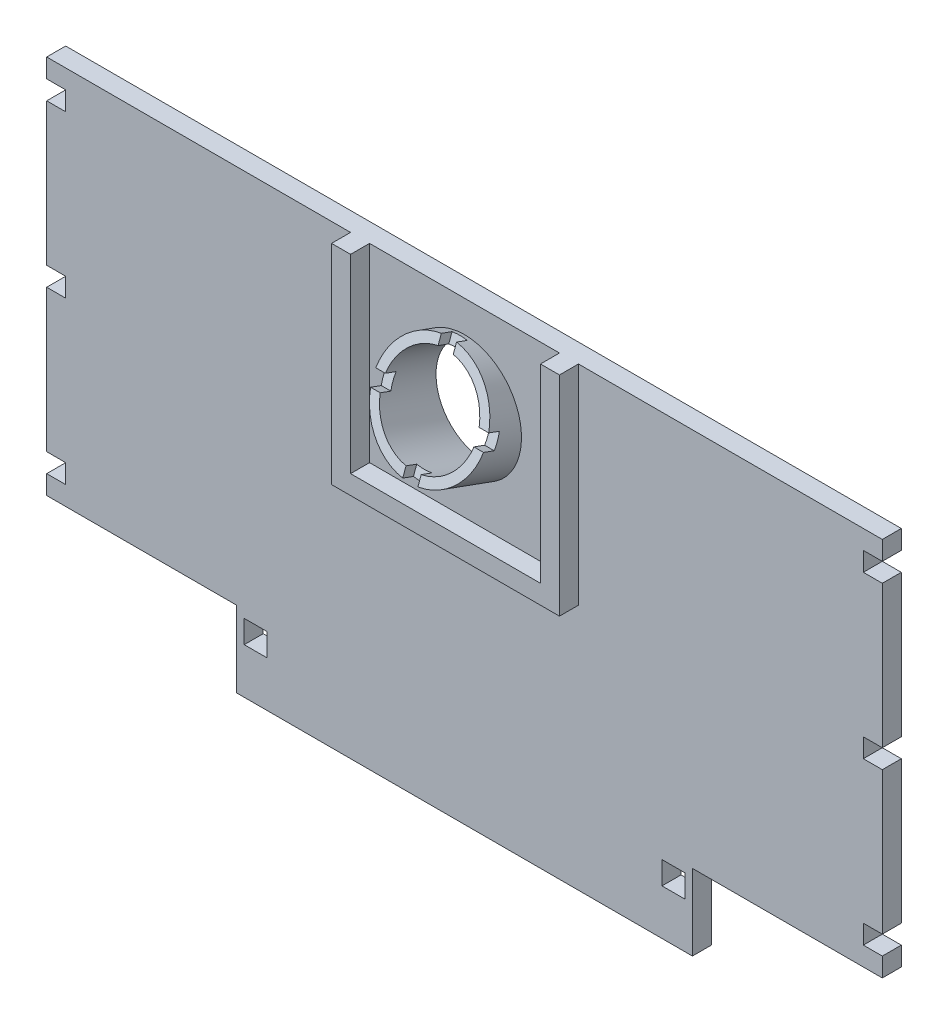
SolidWorks part; units mm, degrees
ref_plane "Front Plane" through (0, 0, 0) normal (0, 0, 1) x (1, 0, 0)
ref_plane "Top Plane" through (0, 0, 0) normal (0, 1, 0) x (1, 0, 0)
ref_plane "Right Plane" through (0, 0, 0) normal (1, 0, 0) x (0, 0, -1)
sketch "Sketch2" plane through (0, 0, 0) normal (0, 0, 1) x (1, 0, 0)
  line L0 (-100, -75) -> (-100, -45)
  line L1 (-100, 75) -> (100, 75)
  line L2 (-100, 75) -> (-100, -75)
  line L3 (-100, -75) -> (100, -75)
  line L4 (100, 75) -> (100, -75)
  line L5 (-100, 75) -> (100, -75) construction
  line L6 (-100, -75) -> (100, 75) construction
  line L7 (-100, -45) -> (-60, -45)
  line L8 (-60, -45) -> (-60, -75)
  line L9 (100, -75) -> (100, -45)
  line L10 (100, -45) -> (60, -45)
  line L11 (60, -45) -> (60, -75)
  line L12 (-60, -75) -> (-60, -65)
  line L13 (-60, -65) -> (60, -65)
  line L14 (-60, -45) -> (-50, -45)
  line L15 (-50, -45) -> (-50, -55)
  line L16 (-50, -55) -> (-60, -55)
  line L17 (60, -45) -> (50, -45)
  line L18 (50, -45) -> (50, -55)
  line L19 (50, -55) -> (60, -55)
  line L20 (-55, -55) -> (-55, -50)
  line L21 (-55, -50) -> (-50, -50)
  line L22 (-50, -45) -> (-52, -45)
  line L23 (-50, -45) -> (-50, -47)
  line L24 (0, -65) -> (0, -61.3332)
  line L25 (-58, -53) -> (-52, -53)
  line L26 (-58, -53) -> (-58, -47)
  line L27 (-58, -47) -> (-52, -47)
  line L28 (-52, -53) -> (-52, -47)
  line L29 (-58, -53) -> (-52, -47) construction
  line L30 (-58, -47) -> (-52, -53) construction
  line L31 (58, -47) -> (52, -47)
  line L32 (52, -53) -> (52, -47)
  line L33 (58, -53) -> (52, -53)
  line L34 (58, -53) -> (58, -47)
  point P0 (0, 0)
  dimension "D1" = 200
  dimension "D2" = 150
  dimension "D3" = 40
extrude "Boss-Extrude1" add sketch "Sketch2" along normal blind 5 contours L19 L18 L17 L10 L4 L1 L2 L7 L14 L15 L16 L8 L13 L11 | L18 L19 L11 L17 L34 L33 L32 L31 | L28 L21 L15 L14 L8 L16 L20 L25 L26 L27 | L28 L25 L20 L16 L15 L21 region at (0, 9.084, 0) region at (-56, -45.1414, 0) region at (-51.9375, -53.0625, 0) region at (55, -54.8586, 0)
sketch "Sketch3" plane through (0, 0, 5) normal (0, 0, 1) x (1, 0, 0)
  line L0 (-100, 75) -> (-100, -45) construction
  line L1 (-100, 75) -> (-100, 55)
  line L2 (-100, 55) -> (100, 55)
  line L3 (100, 75) -> (100, -45) construction
  line L4 (100, 55) -> (100, 75)
  line L5 (100, 75) -> (-100, 75)
extrude "Cut-Extrude1" cut sketch "Sketch3" against normal blind 5
sketch "Sketch4" plane through (0, 0, 0) normal (0, 0, -1) x (-1, 0, 0)
  line L0 (-100, 55) -> (100, 55)
  line L1 (100, 55) -> (100, -45)
  line L2 (100, -45) -> (-100, -45)
  line L3 (-100, -45) -> (-100, 55)
  line L4 (100, 55) -> (95, 55)
  line L5 (95, 55) -> (95, -45)
  line L6 (95, -45) -> (100, -45)
  line L7 (100, 55) -> (100, 45)
  line L8 (100, 45) -> (95, 45)
  line L9 (95, 45) -> (95, 50)
  line L10 (95, 50) -> (100, 50)
  line L11 (100, 50) -> (99, 50)
  line L12 (100, 50) -> (100, 49)
  line L13 (97.5, 45) -> (97.5, 47.5)
  line L14 (100, 5) -> (95, 5)
  line L15 (96, 46) -> (99, 46)
  line L16 (96, 46) -> (96, 49)
  line L17 (96, 49) -> (99, 49)
  line L18 (99, 46) -> (99, 49)
  line L19 (96, 46) -> (99, 49) construction
  line L20 (96, 49) -> (99, 46) construction
  line L21 (96, -39) -> (99, -39)
  line L22 (99, -36) -> (99, -39)
  line L23 (96, -36) -> (99, -36)
  line L24 (96, -36) -> (96, -39)
  line L25 (100, 5) -> (100, 7.5)
  line L26 (100, 5) -> (100, 2.5)
  line L27 (100, 2.5) -> (95, 2.5)
  line L28 (95, 2.5) -> (95, 7.5)
  line L29 (95, 7.5) -> (100, 7.5)
  line L30 (100, 2.5) -> (99, 2.5)
  line L31 (100, 2.5) -> (100, 3.5)
  line L32 (0, -45) -> (0, -36)
  line L33 (96, 6.5) -> (99, 6.5)
  line L34 (96, 6.5) -> (96, 3.5)
  line L35 (96, 3.5) -> (99, 3.5)
  line L36 (99, 6.5) -> (99, 3.5)
  line L37 (96, 6.5) -> (99, 3.5) construction
  line L38 (96, 3.5) -> (99, 6.5) construction
  line L39 (97.5, -36) -> (97.5, -39)
  line L40 (100, 50) -> (95, 50)
  line L41 (100, 50) -> (100, 45)
  line L42 (100, 45) -> (95, 45)
  line L43 (95, 50) -> (95, 45)
  line L44 (100, 50) -> (95, 45) construction
  line L45 (100, 45) -> (95, 50) construction
  line L46 (97.5, -39) -> (97.5, -40)
  line L47 (-100, 45) -> (-95, 45)
  line L48 (100, -35) -> (95, -35)
  line L49 (100, -35) -> (100, -40)
  line L50 (100, -40) -> (95, -40)
  line L51 (95, -35) -> (95, -40)
  line L52 (100, -35) -> (95, -40) construction
  line L53 (100, -40) -> (95, -35) construction
  line L54 (-95, 50) -> (-95, 45)
  line L55 (-100, 50) -> (-95, 50)
  line L56 (-100, 50) -> (-100, 45)
  line L57 (-100, 5) -> (-100, 7.5)
  line L58 (-95, 7.5) -> (-100, 7.5)
  line L59 (-95, 2.5) -> (-95, 7.5)
  line L60 (-100, 2.5) -> (-95, 2.5)
  line L61 (-100, 5) -> (-100, 2.5)
  line L62 (-100, -40) -> (-95, -40)
  line L63 (-95, -35) -> (-95, -40)
  line L64 (-100, -35) -> (-95, -35)
  line L65 (-100, -35) -> (-100, -40)
  point P31 (97.5, 5)
  point P44 (97.5, -37.5)
sketch "Sketch6" plane through (0, 0, 0) normal (0, 0, -1) x (-1, 0, 0)
  line L0 (0, -65) -> (0, -45)
  line L1 (60, -65) -> (-60, -65) construction
  line L2 (0, -45) -> (50, -45)
  line L3 (50, -45) -> (50, -65)
  line L4 (0, -45) -> (-50, -45)
  line L5 (-50, -45) -> (-50, -65)
  line L6 (-50, -45) -> (-60, -45)
  line M21 (-60, -65) -> (60, -65)
extrude "Boss-Extrude2" add sketch "Sketch6" along normal blind 100 contours L3 L2 L0 M21 | L4 L5 L0 M21 region at (25, -55, 0) region at (-25, -55, 0)
sketch "Sketch8" plane through (50, 0, 0) normal (1, 0, 0) x (0, 0, -1)
  line L0 (100, -45) -> (100, 55)
  line L1 (100, 55) -> (78.5761, 55)
  line L2 (100, -45) -> (42.1791, -45)
  line L3 (100, -45) -> (0, -45) construction
  line L4 (78.5761, 55) -> (42.1791, -45)
  line L5 (60.3776, 5) -> (63.7978, 14.3969)
  line L6 (60.3776, 5) -> (56.9574, -4.3969)
  line M8 (100, -45) -> (0, -45)
  dimension "D1" = 21.4239
  dimension "D2" = 57.8209
extrude "Boss-Extrude3" add sketch "Sketch8" against normal blind 100 contours L1 L4 L0 M8 region at (50, -2.655, -78.7957)
sketch "Sketch12" plane through (50, 0, 0) normal (1, 0, 0) x (0, 0, -1)
  line L0 (42.1791, -45) -> (78.5761, 55)
  line L2 (42.1791, -45) -> (100, -45)
  line L3 (100, 55) -> (100, -65) construction
  line L4 (100, -45) -> (100, 55)
  line L5 (78.5761, 55) -> (83.897, 55)
  line L6 (100, 55) -> (78.5761, 55) construction
  line L7 (83.897, 55) -> (88.897, 55)
  line L8 (83.897, 55) -> (47.5, -45)
  line L9 (88.897, 55) -> (52.5, -45)
  line M5 (100, 55) -> (78.5761, 55)
  line M6 (78.5761, 55) -> (42.1791, -45)
  dimension "D1" = 5.3209
extrude "Cut-Extrude4" cut sketch "Sketch12" against normal blind 100 contours L8 L2 M5 M6 region at (50, 5, -63.0381)
sketch "Sketch13" plane through (0, -20.5302, -56.4063) normal (0, 0.342, 0.9397) x (1, 0, 0)
  line L0 (-50, 80.3776) -> (50, 80.3776)
  line L1 (50, 80.3776) -> (50, -26.0402)
  line L2 (50, -26.0402) -> (-50, -26.0402)
  line L3 (-50, -26.0402) -> (-50, 80.3776)
  line L4 (0, 80.3776) -> (0, 27.1687)
  circle A0 centre (0, 27.1687) radius 10
extrude "Boss-Extrude5" add sketch "Sketch13" along normal blind 100 contours A0 region at (6.8711, 11.4567, -68.0486)
sketch "Sketch14" plane through (0, 13.6718, 37.563) normal (0, 0.342, 0.9397) x (1, 0, 0)
  circle A0 centre (0, 27.1687) radius 10.3
  circle A1 centre (0, 27.1687) radius 12.5
  circle M3 centre (0, 27.1687) radius 10
  dimension "D1" = 25
extrude "Cut-Extrude5" cut sketch "Sketch14" against normal blind 100 contours M3 | A1 M3 | A0 M3 | A0 | A1 region at (-10.0087, 39.202, 28.2708) region at (-12.1464, 39.202, 28.2708) region at (0, 39.202, 28.2708)
ref_plane "Plane1" through (0, 13.6718, 37.563) normal (0, 0.342, 0.9397) x (1, 0, 0)
sketch "Sketch15" plane through (0, 13.6718, 37.563) normal (0, 0.342, 0.9397) x (1, 0, 0)
  circle A0 centre (0, 27.1687) radius 10
  circle A1 centre (0, 27.1687) radius 12.5
  circle A2 centre (0, 27.1687) radius 15
ref_plane "Plane2" through (0, 0, -30) normal (0, 0, -1) x (-1, 0, 0)
extrude "Boss-Extrude6" add sketch "Sketch15" against normal blind 40 contours A2 A1 region at (-14.5757, 39.202, 28.2708)
sketch "Sketch16" plane through (0, 0, -30) normal (0, 0, -1) x (-1, 0, 0)
  line L0 (0, 61.0723) -> (0, 0)
  line L1 (0, 0) -> (25, 0)
  line L2 (25, 0) -> (25, 61.0723)
  line L3 (25, 61.0723) -> (-25, 61.0723)
  line L4 (-25, 61.0723) -> (-25, 0)
  line L5 (-25, 0) -> (0, 0)
sketch "Sketch17" plane through (0, 13.6718, 37.563) normal (0, 0.342, 0.9397) x (1, 0, 0)
  circle A0 centre (0, 27.1687) radius 10.3
  circle A1 centre (0, 27.1687) radius 12.5
extrude "Cut-Extrude10" cut sketch "Sketch16" against normal blind 35 contours L4 L5 L0 L3 | L2 L3 L0 L1 region at (-12.5, 30.5361, -30) region at (12.5, 30.5361, -30)
sketch "Sketch18" plane through (0, 0, 5) normal (0, 0, 1) x (1, 0, 0)
  line L0 (25, 55) -> (25, 0)
  line L1 (25, 0) -> (-25, 0)
  line L2 (-25, 0) -> (-25, 55)
  line L3 (-25, 55) -> (25, 55)
  line L4 (-30, 55) -> (-30, 60)
  line L5 (30, 0) -> (30, 55)
  line L6 (25, 55) -> (100, 55) construction
  line L7 (30, 55) -> (25, 55)
  line L8 (30, 0) -> (30, -5)
  line L9 (30, -5) -> (-30, -5)
  line L10 (-30, -5) -> (-30, 55)
  line L11 (-100, 55) -> (-25, 55) construction
  line L12 (-30, 55) -> (-25, 55)
  line L13 (-30, 60) -> (30, 60)
  line L14 (30, 60) -> (30, 55)
  line L15 (-30, 55) -> (30, 55)
  line M5 (25, 55) -> (25, 0)
  line M6 (25, 0) -> (-25, 0)
  line M7 (-25, 0) -> (-25, 55)
  line M8 (-25, 55) -> (-100, 55)
  line M40 (100, 55) -> (25, 55)
sketch "Sketch20" plane through (0, 0, 5) normal (0, 0, -1) x (-1, 0, 0)
  ellipse E2 centre (0, 30.7322) end of major axis (0, 44.0344) minor radius 12.5 (0, 44.0344) -> (0, 44.0344) ccw
  ellipse E3 centre (0, 30.7322) end of major axis (0, 44.0344) minor radius 12.5
  ellipse E5 centre (0, 30.7322) end of major axis (0, 46.6948) minor radius 15 (0, 46.6948) -> (0, 46.6948) ccw
  ellipse E6 centre (0, 30.7322) end of major axis (0, 46.6948) minor radius 15
  dimension "D1" = 0
  dimension "D2" = 0
sketch "Sketch21" plane through (0, 0, -30) normal (0, 0, -1) x (-1, 0, 0)
  line L0 (0, 30.7322) -> (0, 46.6948)
  line L1 (0, 46.6948) -> (-15, 46.6948)
  line L2 (-15, 46.6948) -> (-15, 14.7695)
  line L3 (-15, 14.7695) -> (15, 14.7695)
  line L4 (15, 14.7695) -> (15, 46.6948)
  line L5 (15, 46.6948) -> (0, 46.6948)
  line L6 (-25, 55) -> (-25, 0)
  line L7 (-25, 0) -> (25, 0)
  line L8 (25, 0) -> (25, 55)
  line L9 (25, 55) -> (-25, 55)
  line L10 (-30, 55) -> (-30, 60)
  line L11 (-30, 60) -> (-25, 60)
  line L12 (-25, 60) -> (30, 60)
  line L13 (30, 60) -> (30, 55)
  line L14 (30, 55) -> (30, -5)
  line L15 (30, -5) -> (-30, -5)
  line L16 (-30, -5) -> (-30, 55)
  line L17 (-25, 55) -> (-30, 55)
  line L18 (25, 55) -> (30, 55)
  line L19 (-25, 55) -> (25, 55)
  ellipse E2 centre (0, 30.7322) end of major axis (0, 46.6948) minor radius 15
  ellipse E3 centre (0, 30.7322) end of major axis (0, 46.6948) minor radius 15
  ellipse E5 centre (0, 30.7322) end of major axis (0, 44.0344) minor radius 12.5
  ellipse E6 centre (0, 30.7322) end of major axis (0, 44.0344) minor radius 12.5
  dimension "D1" = 0
  dimension "D2" = 0
extrude "Cut-Extrude11" cut sketch "Sketch15<4>" against normal blind 15 contours A2 A1 region at (-14.5757, 39.202, 28.2708)
sketch "Sketch15<4>" plane through (0, 13.6718, 37.563) normal (0, 0.342, 0.9397) x (1, 0, 0) same geometry as "Sketch15"
sketch "Sketch22" plane through (0, 0, 0) normal (0, 0, -1) x (-1, 0, 0)
  line L0 (30, -5) -> (-30, -5)
  line L1 (-30, -5) -> (-30, 60)
  line L2 (-30, 60) -> (30, 60)
  line L3 (30, 60) -> (30, -5)
  line L4 (25, 0) -> (-25, 0)
  line L5 (-25, 0) -> (-25, 55)
  line L6 (-25, 55) -> (25, 55)
  line L7 (25, 55) -> (25, 0)
  line L8 (-25, 55) -> (-30, 55)
  line L9 (-25, 55) -> (-100, 55) construction
  line L10 (25, 55) -> (30, 55)
  line L11 (30, -5) -> (30, 55) construction
  line L12 (25, 0) -> (30, 0)
  line L13 (-25, 0) -> (-30, 0)
  line M17 (25, 0) -> (-25, 0)
  line M18 (-25, 0) -> (-25, 55)
  line M56 (25, 55) -> (25, 0)
extrude "Boss-Extrude7" add sketch "Sketch18" along normal blind 5 contours L10 L9 L8 L5 M40 M5 M6 M7 M8 region at (27.5, 54.1515, 5)
sketch "Sketch23" plane through (0, 8.5415, 23.4676) normal (0, 0.342, 0.9397) x (1, 0, 0)
  circle A0 centre (0, 27.1687) radius 15
  circle A1 centre (0, 27.1687) radius 10.3
  circle A2 centre (0, 27.1687) radius 12.5
  circle M4 centre (0, 27.1687) radius 12.5
  circle M5 centre (0, 27.1687) radius 15
extrude "Boss-Extrude8" add sketch "Sketch23" against normal blind 25 contours M5 M4 region at (-14.5757, 34.0717, 14.1754)
extrude "Cut-Extrude12" cut sketch "Sketch21" against normal blind 35 contours E6 E3 | E6 | L8 L9 L6 L7 L5 L4 L3 L2 L1 | E3 L4 L5 | E3 L1 L2 | E3 L2 L3 | E3 L3 L4 region at (-10.4462, 41.5478, -30) region at (11.6495, 43.1293, -30) region at (-11.6495, 43.1293, -30) region at (0, 17.795, -30) region at (11.6495, 18.335, -30) region at (-11.6495, 18.335, -30) region at (0, 54.2567, -30)
extrude "Boss-Extrude9" add sketch "Sketch22" against normal blind 5 contours L6 M18 M17 M56 region at (0, 27.5, 0)
extrude "Cut-Extrude13" cut sketch "Sketch23<3>" against normal blind 20 contours A1 M4 | A1 region at (0, 34.0717, 14.1754) region at (-12.1464, 34.0717, 14.1754)
sketch "Sketch23<3>" plane through (0, 8.5415, 23.4676) normal (0, 0.342, 0.9397) x (1, 0, 0) same geometry as "Sketch23"
sketch "Sketch27" plane through (0, 8.5415, 23.4676) normal (0, 0.342, 0.9397) x (1, 0, 0)
  line L1 (-2, 42.1687) -> (2, 42.1687)
  line L2 (-2, 42.1687) -> (-2, 12.1687)
  line L3 (-2, 12.1687) -> (2, 12.1687)
  line L4 (2, 42.1687) -> (2, 12.1687)
  line L5 (-2, 42.1687) -> (2, 12.1687) construction
  line L6 (-2, 12.1687) -> (2, 42.1687) construction
  line L7 (-15, 29.1687) -> (15, 29.1687)
  line L8 (-15, 29.1687) -> (-15, 25.1687)
  line L9 (-15, 25.1687) -> (15, 25.1687)
  line L10 (15, 29.1687) -> (15, 25.1687)
  line L11 (-15, 29.1687) -> (15, 25.1687) construction
  line L12 (-15, 25.1687) -> (15, 29.1687) construction
  circle A0 centre (0, 27.1687) radius 12.5
  circle A1 centre (0, 27.1687) radius 15
  point P0 (0, 27.1687)
  point P6 (0, 27.1687)
  circle M8 centre (0, 27.1687) radius 12.5
  circle M9 centre (0, 27.1687) radius 15
  dimension "D1" = 4
  dimension "D2" = 4
  dimension "D3" = 30
  dimension "D4" = 30
extrude "Cut-Extrude15" cut sketch "Sketch27" against normal blind 3 contours L4 L2 M9 M8 | L9 L7 M8 M9 | L9 L7 M9 M8 | L4 L2 M8 M9 region at (0, 46.9463, 9.4894) region at (-13.7008, 34.0717, 14.1754) region at (13.7008, 34.0717, 14.1754) region at (0, 21.1972, 18.8613)
sketch "Sketch28" plane through (0, 0, 10) normal (0, 0, 1) x (1, 0, 0)
  line L0 (-25, 55) -> (-25, 5)
  line L1 (-25, 55) -> (-25, 0) construction
  line L2 (-25, 5) -> (25, 5)
  line L3 (25, 55) -> (25, 0) construction
  line L4 (25, 5) -> (25, 0)
  line L5 (25, 0) -> (-25, 0)
  line L6 (-25, 0) -> (-25, 5)
  line L7 (-25, 0) -> (-30, 0)
  line L8 (-30, -5) -> (-30, 55) construction
  line L9 (-30, 0) -> (-30, -5)
  line L10 (-30, -5) -> (30, -5)
  line L11 (30, -5) -> (30, 0)
  line L12 (30, 55) -> (30, -5) construction
  line L13 (30, 0) -> (25, 0)
  line M1 (-30, 55) -> (-30, -5)
  line M2 (-30, -5) -> (30, -5)
  line M3 (30, -5) -> (30, 55)
  line M5 (25, 55) -> (25, 0)
  line M6 (25, 0) -> (-25, 0)
  line M7 (-25, 0) -> (-25, 55)
extrude "Cut-Extrude16" cut sketch "Sketch28" against normal blind 5 contours L13 L7 M3 M6 M1 M2 region at (0, -2.5, 10)
extrude "Boss-Extrude12" add sketch "Sketch28<3>" against normal blind 5 contours L2 M7 M6 M5 region at (0, 2.5, 10)
sketch "Sketch28<3>" plane through (0, 0, 10) normal (0, 0, 1) x (1, 0, 0) same geometry as "Sketch28"
sketch "Sketch30" plane through (0, 0, -100) normal (0, 0, -1) x (-1, 0, 0)
  line L0 (-100, 55) -> (100, 55)
  line L1 (100, 55) -> (100, -65)
  line L2 (100, -65) -> (-100, -65)
  line L3 (-100, -65) -> (-100, 55)
extrude "Cut-Extrude17" cut sketch "Sketch30" against normal blind 100
sketch "Sketch31" plane through (0, 0, 0) normal (0, 0, -1) x (-1, 0, 0)
  line L0 (-100, 55) -> (100, 55)
  line L1 (100, 55) -> (110, 55)
  line L2 (110, 55) -> (110, -45)
  line L3 (110, -45) -> (100, -45)
  line L4 (100, -45) -> (100, 55)
  line L5 (-100, 55) -> (-110, 55)
  line L6 (-110, 55) -> (-110, -45)
  line L7 (-110, -45) -> (-100, -45)
  line L8 (-100, 55) -> (-100, -45)
  line L9 (-105, 50) -> (-110, 50)
  line L10 (-105, 45) -> (-110, 45)
  line L11 (-110, 45) -> (-105, 45)
  line L12 (-105, 45) -> (-105, 50)
  line L13 (-105, 7.5) -> (-110, 7.5)
  line L14 (-110, 7.5) -> (-110, 2.5)
  line L15 (-110, 2.5) -> (-105, 2.5)
  line L16 (-110, 7.5) -> (-105, 7.5)
  line L17 (-105, 7.5) -> (-105, 2.5)
  line L18 (-105, -35) -> (-110, -35)
  line L19 (-105, -40) -> (-110, -40)
  line L20 (-110, -35) -> (-105, -35)
  line L21 (-105, -35) -> (-105, -40)
  line L22 (0, -45) -> (0, -36)
  line L23 (100, -45) -> (-100, -45) construction
  line L24 (105, -40) -> (110, -40)
  line L25 (105, -35) -> (105, -40)
  line L26 (105, -35) -> (110, -35)
  line L27 (110, 2.5) -> (105, 2.5)
  line L28 (105, 7.5) -> (105, 2.5)
  line L29 (105, 7.5) -> (110, 7.5)
  line L30 (105, 45) -> (110, 45)
  line L31 (105, 45) -> (105, 50)
  line L32 (105, 50) -> (110, 50)
  line M14 (100, -45) -> (100, 55)
  line M28 (-100, 55) -> (-100, -45)
extrude "Boss-Extrude13" add sketch "Sketch31" against normal blind 5 contours L31 L32 L2 L1 L3 L24 L25 L26 L27 L28 L29 L30 M14 | L18 L21 L19 L6 L7 L5 L9 L12 L10 L13 L17 L15 M28 region at (-104.7973, 5, 0) region at (104.7973, 5, 0)
